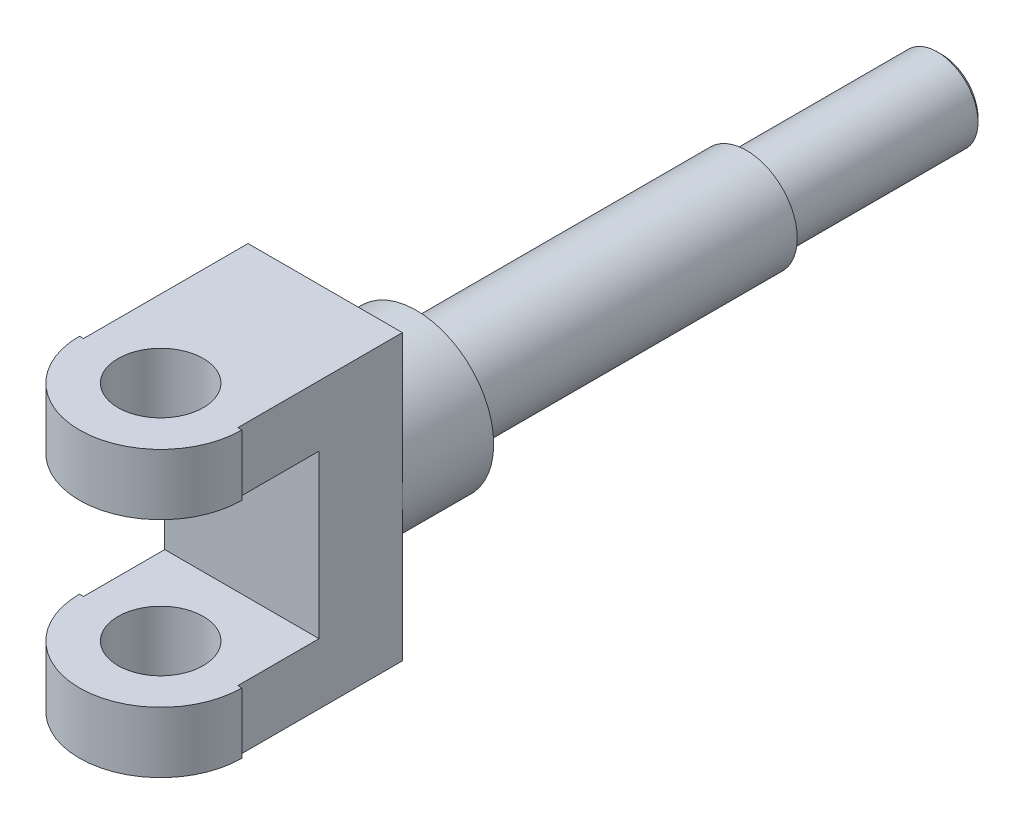
SolidWorks part; units mm, degrees
ref_plane "Front Plane" through (0, 0, 0) normal (0, 0, 1) x (1, 0, 0)
ref_plane "Top Plane" through (0, 0, 0) normal (0, 1, 0) x (1, 0, 0)
ref_plane "Right Plane" through (0, 0, 0) normal (1, 0, 0) x (0, 0, -1)
sketch "Esquisse2" plane through (0, 0, 0) normal (0, 0, 1) x (1, 0, 0)
  circle A0 centre (0, 0) radius 10
  dimension "D1" = 20
extrude "Boss.-Extru.1" add sketch "Esquisse2" along normal blind 48
sketch "Esquisse3" plane through (0, 0, 48) normal (0, 0, 1) x (1, 0, 0)
  circle A0 centre (0, 0) radius 12.5
  dimension "D1" = 25
extrude "Boss.-Extru.2" add sketch "Esquisse3" along normal blind 81.25
chamfer "Chanfrein1" distance 1 angle 45 1 edges at (10, 0, 0)
sketch "Esquisse6" plane through (0, 0, 129.25) normal (0, 0, 1) x (1, 0, 0)
  circle A0 centre (0, 0) radius 19
  dimension "D1" = 38
extrude "Boss.-Extru.3" add sketch "Esquisse6" along normal blind 60
sketch "Esquisse7" plane through (0, 0, 0) normal (0, 1, 0) x (1, 0, 0)
  line L0 (0, -129.25) -> (0, -109.25) construction
  line L1 (19, -129.25) -> (-19, -129.25) construction
  line L2 (0, -109.25) -> (-47.9201, -192.25) construction
  line L3 (-19, -129.25) -> (-19, -189.25) construction
  line L4 (-19, -129.25) -> (-19, -189.25) construction
  line L5 (0, -109.25) -> (47.9201, -192.25) construction
  line L6 (-19, -171.9902) -> (19, -171.9902) construction
  line L11 (-19, -151.7304) -> (19, -151.7304)
  line L12 (-19, -151.7304) -> (-19, -192.25)
  line L13 (-19, -192.25) -> (19, -192.25)
  line L14 (19, -151.7304) -> (19, -192.25)
  line L15 (0, -189.25) -> (0, -129.25) construction
  point P16 (0, -171.9902)
  point P19 (0, 0)
  point P20 (0, 0)
  dimension "D1" = 20
  dimension "D2" = 30
  dimension "D3" = 83
  dimension "D4" = 38
extrude "Boss.-Extru.4" add sketch "Esquisse7" along normal blind 35 and the other way blind 35
sketch "Esquisse12" plane through (0, 35, 0) normal (0, 1, 0) x (1, 0, 0)
  line L0 (-19, -192.25) -> (19, -192.25) construction
  line L1 (-10.5, -192.25) -> (10.5, -192.25)
  arc A0 (-10.5, -192.25) -> (10.5, -192.25) centre (0, -192.25) cw
  dimension "D1" = 10.5
extrude "Enlèv. mat.-Extru.3" cut sketch "Esquisse12" against normal up to next
sketch "Esquisse15" plane through (0, 35, 0) normal (0, 1, 0) x (1, 0, 0)
  line L0 (-19, -192.25) -> (19, -192.25) construction
  line L1 (-20, -192.25) -> (-10.5, -192.25)
  line L2 (10.5, -192.25) -> (20, -192.25)
  arc A0 (-10.5, -192.25) -> (10.5, -192.25) centre (0, -192.25) ccw
  arc A1 (20, -192.25) -> (-20, -192.25) centre (0, -192.25) cw
  point P8 (0, 0)
  point P9 (0, 0)
  point P10 (0, 0)
  dimension "D1" = 20
sketch "Esquisse16" plane through (0, 0, 192.25) normal (0, 0, 1) x (1, 0, 0)
  line L0 (-19, -20) -> (-19, 20) construction
  line L1 (-19, 20) -> (19, 20)
  line L2 (-19, 20) -> (-19, -20)
  line L3 (-19, -20) -> (19, -20)
  line L4 (19, 20) -> (19, -20)
  line L5 (19, -20) -> (19, 20) construction
  point P8 (19, 0)
  dimension "D1" = 40
extrude "Boss.-Extru.6" add sketch "Esquisse15" against normal blind 15
extrude "Enlèv. mat.-Extru.4" cut sketch "Esquisse16" against normal blind 20
mirror "Symétrie2" about plane through (0, 0, 0) normal (0, 1, 0) of "Boss.-Extru.6"
